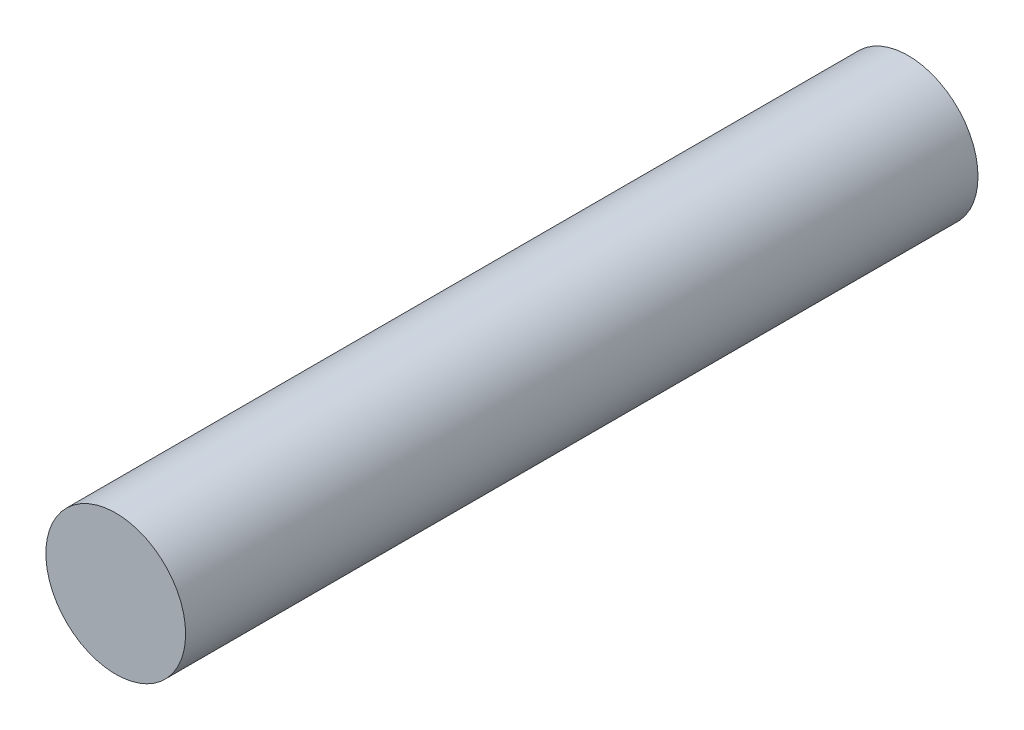
SolidWorks part; units mm, degrees
ref_plane "Front Plane" through (0, 0, 0) normal (0, 0, 1) x (1, 0, 0)
ref_plane "Top Plane" through (0, 0, 0) normal (0, 1, 0) x (1, 0, 0)
ref_plane "Right Plane" through (0, 0, 0) normal (1, 0, 0) x (0, 0, -1)
sketch "Sketch1" plane through (0, 0, 0) normal (0, 0, 1) x (1, 0, 0)
  circle A0 centre (0, 0) radius 5
  dimension "D1" = 10
extrude "Boss-Extrude1" add sketch "Sketch1" along normal blind 56.7
